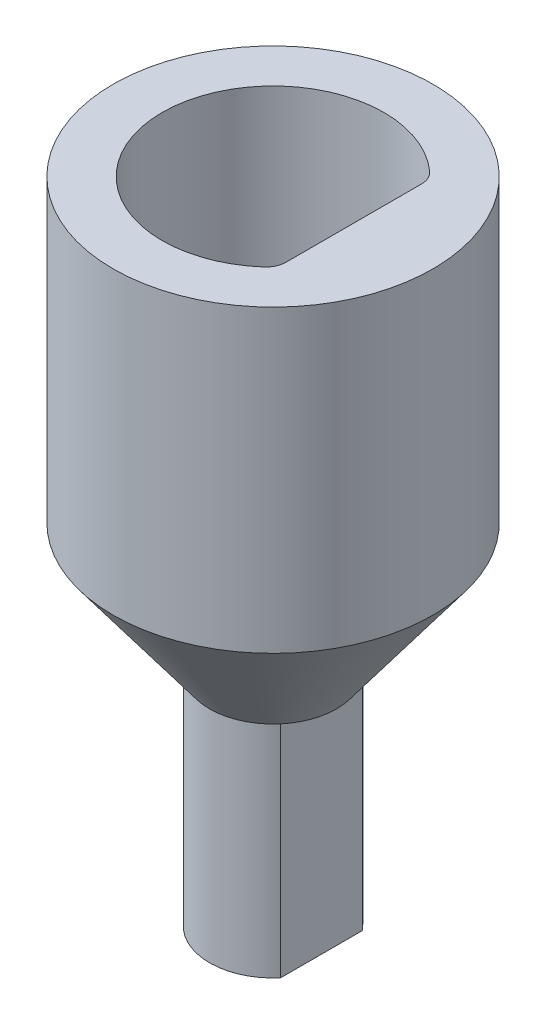
SolidWorks part; units mm, degrees
ref_plane "Front Plane" through (0, 0, 0) normal (0, 0, 1) x (1, 0, 0)
ref_plane "Top Plane" through (0, 0, 0) normal (0, 1, 0) x (1, 0, 0)
ref_plane "Right Plane" through (0, 0, 0) normal (1, 0, 0) x (0, 0, -1)
sketch "Sketch1" plane through (0, 0, 0) normal (0, 1, 0) x (1, 0, 0)
  line L1 (4.0364, -0.0001) -> (4.0364, 3.8092)
  line L2 (4.0364, -0.0001) -> (4.0364, -3.8092)
  arc A0 (4.0364, 3.8092) -> (4.0364, -3.8092) centre (0, 0) ccw
  circle A1 centre (0, 0) radius 8
  dimension "D1" = 11.1
  dimension "D2" = 16
extrude "Boss-Extrude1" add sketch "Sketch1" along normal blind 10
sketch "Sketch2" plane through (0, 0, 0) normal (0, 0, 1) x (1, 0, 0)
  line L0 (8, 0) -> (8, -5)
  line L1 (3.175, -22.4737) -> (0, -22.4737)
  line L2 (8, -5) -> (3.175, -11.4737)
  line L3 (3.175, -11.4737) -> (3.175, -22.4737)
  line L4 (0, -22.4737) -> (0, 0)
  line L5 (0, -22.4737) -> (0, -30.3228) construction
  line L6 (8, 0) -> (0, 0)
  dimension "D1" = 5
  dimension "D3" = 11
revolve "Revolve1" add sketch "Sketch2" angle 360 about L5
sketch "Sketch3" plane through (0, 0, 0) normal (0, 0, 1) x (1, 0, 0)
  line L0 (3.175, -22.4737) -> (2.425, -22.4737)
  line L1 (-3.175, -22.4737) -> (3.175, -22.4737) construction
  line L2 (2.425, -22.4737) -> (2.425, -11.4737)
  line L3 (3.175, -11.4737) -> (-3.175, -11.4737) construction
  line L4 (2.425, -11.4737) -> (3.175, -11.4737)
  line L5 (3.175, -11.4737) -> (3.175, -22.4737)
  dimension "D1" = 0.75
extrude "Cut-Extrude1" cut sketch "Sketch3" against normal blind 12 and the other way blind 12
fillet "Fillet2" radius 1 1 edges at (4.0364, 5, -3.8092)
fillet "Fillet3" radius 1 1 edges at (4.0364, 5, 3.8092)
